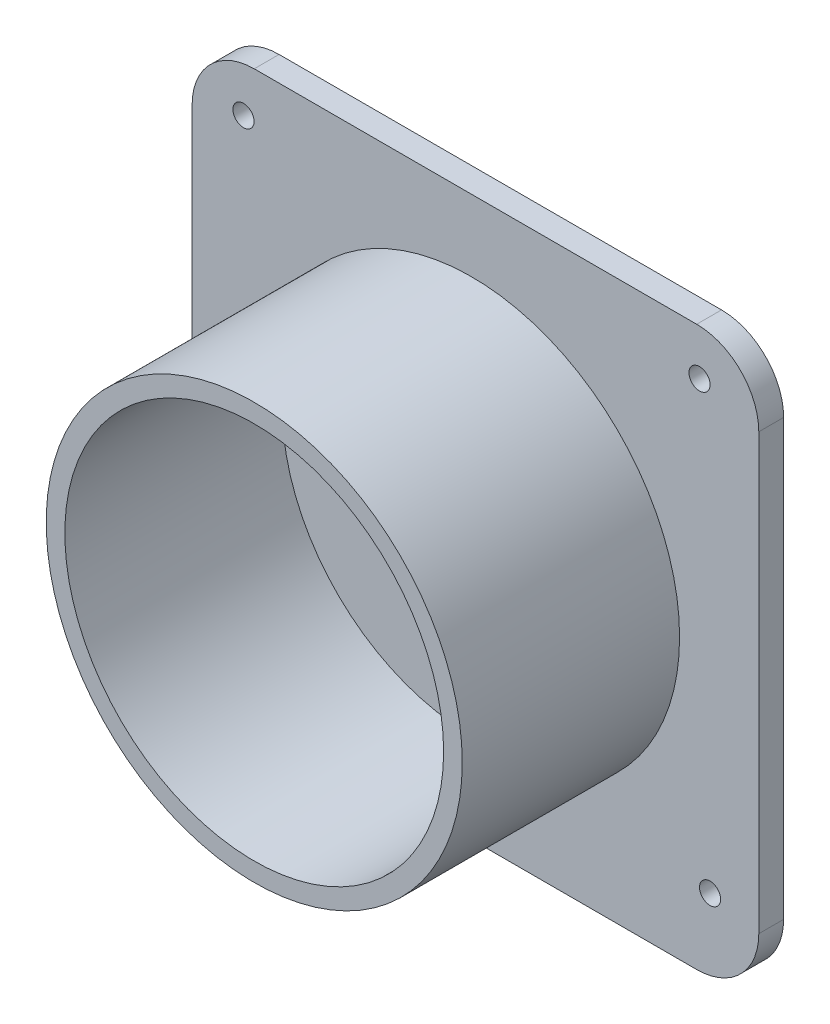
SolidWorks part; units mm, degrees
ref_plane "Front Plane" through (0, 0, 0) normal (0, 0, 1) x (1, 0, 0)
ref_plane "Top Plane" through (0, 0, 0) normal (0, 1, 0) x (1, 0, 0)
ref_plane "Right Plane" through (0, 0, 0) normal (1, 0, 0) x (0, 0, -1)
sketch "Sketch1" plane through (0, 0, 0) normal (0, 0, 1) x (1, 0, 0)
  line L0 (-65.6842, 45.5839) -> (65.586, 45.5839)
  line L1 (-85.0491, 50.5839) -> (84.9509, 50.5839)
  line L2 (-85.0491, 50.5839) -> (-85.0491, -39.4161)
  line L3 (-85.0491, -39.4161) -> (84.9509, -39.4161)
  line L4 (84.9509, 50.5839) -> (84.9509, -39.4161)
  line L8 (79.9509, 31.219) -> (79.9509, -20.0511)
  line L9 (-65.6842, -34.4161) -> (65.586, -34.4161)
  line L10 (-80.0491, 31.219) -> (-80.0491, -20.0511)
  circle A0 centre (-40.0491, 5.5839) radius 30.5
  circle A1 centre (-40.0491, 5.5839) radius 33.5
  arc A3 (-80.0491, 31.219) -> (-65.6842, 45.5839) centre (-85.0491, 50.5839) ccw
  arc A4 (65.586, 45.5839) -> (79.9509, 31.219) centre (84.9509, 50.5839) ccw
  arc A5 (79.9509, -20.0511) -> (65.586, -34.4161) centre (84.9509, -39.4161) ccw
  arc A6 (-65.6842, -34.4161) -> (-80.0491, -20.0511) centre (-85.0491, -39.4161) ccw
  circle A8 centre (-77.3061, 42.8273) radius 3
  circle A9 centre (-77.3061, 42.8273) radius 1.7
  circle A10 centre (75.3915, 41.4665) radius 3
  circle A11 centre (75.3915, 41.4665) radius 1.7
  circle A12 centre (75.3915, -30.5313) radius 3
  circle A13 centre (75.3915, -30.5313) radius 1.7
  circle A14 centre (-77.3061, -32.2313) radius 3
  circle A15 centre (-77.3061, -32.2313) radius 1.7
  point P8 (75.3915, 41.4665)
  dimension "D3" = 61
  dimension "D5" = 3
  dimension "D1" = 90
  dimension "D2" = 170
  dimension "D4" = 45
  dimension "D6" = 45
  dimension "D10" = 5
extrude "Boss-Extrude1" add sketch "Sketch1" against normal blind 5 contours L1 L4 L3 L2
extrude "Boss-Extrude2" add sketch "Sketch1<3>" against normal blind 10 contours L4 L1 L2 L3 A14 A12 A10 A8 L9 A6 L10 A3 L0 A4 L8 A5 region at (-0.0491, 48.6604, 0)
sketch "Sketch1<3>" plane through (0, 0, 0) normal (0, 0, 1) x (1, 0, 0) same geometry as "Sketch1"
extrude "Boss-Extrude3" add sketch "Sketch1<4>" along normal blind 35 contours A1 A0 region at (-72.6016, 5.5839, 0)
sketch "Sketch1<4>" plane through (0, 0, 0) normal (0, 0, 1) x (1, 0, 0) same geometry as "Sketch1"
extrude "Boss-Extrude4" add sketch "Sketch1<7>" against normal blind 10 contours A6 L9 A5 L8 A4 L0 A3 L10 A1 region at (16.1435, 5.5839, 0)
sketch "Sketch1<7>" plane through (0, 0, 0) normal (0, 0, 1) x (1, 0, 0) same geometry as "Sketch1"
sketch "Sketch3" plane through (0, 0, 0) normal (0, 0, 1) x (1, 0, 0)
  line L0 (-85.0491, -39.4161) -> (84.9509, -39.4161) construction
  line L1 (84.9509, 50.5839) -> (6.2046, 50.5839)
  line L2 (84.9509, 50.5839) -> (84.9509, -39.4161)
  line L3 (84.9509, -39.4161) -> (6.2046, -39.4161)
  line L4 (6.2046, 50.5839) -> (6.2046, -39.4161)
extrude "Cut-Extrude3" cut sketch "Sketch3" against normal blind 10
sketch "Sketch5" plane through (0, 0, 0) normal (0, 0, 1) x (1, 0, 0)
  circle A0 centre (-76.778, 43.2074) radius 1.7
  circle A1 centre (-3.3406, 43.2074) radius 1.7
  circle A2 centre (-76.778, -29.3999) radius 1.7
  circle A3 centre (-1.6406, -27.6999) radius 1.7
extrude "Cut-Extrude4" cut sketch "Sketch5" against normal blind 10
sketch "Sketch6" plane through (0, 0, -10) normal (0, 0, -1) x (-1, 0, 0)
  line L1 (-6.2046, 50.5839) -> (85.0491, 50.5839)
  line L2 (-6.2046, 50.5839) -> (-6.2046, -39.4161)
  line L3 (-6.2046, -39.4161) -> (85.0491, -39.4161)
  line L4 (85.0491, 50.5839) -> (85.0491, -39.4161)
extrude "Cut-Extrude5" cut sketch "Sketch6" against normal blind 6
fillet "Fillet2" radius 10 4 edges at (-85.0491, -39.4161, -2) (6.2046, -39.4161, -2) (6.2046, 50.5839, -2) (-85.0491, 50.5839, -2)
